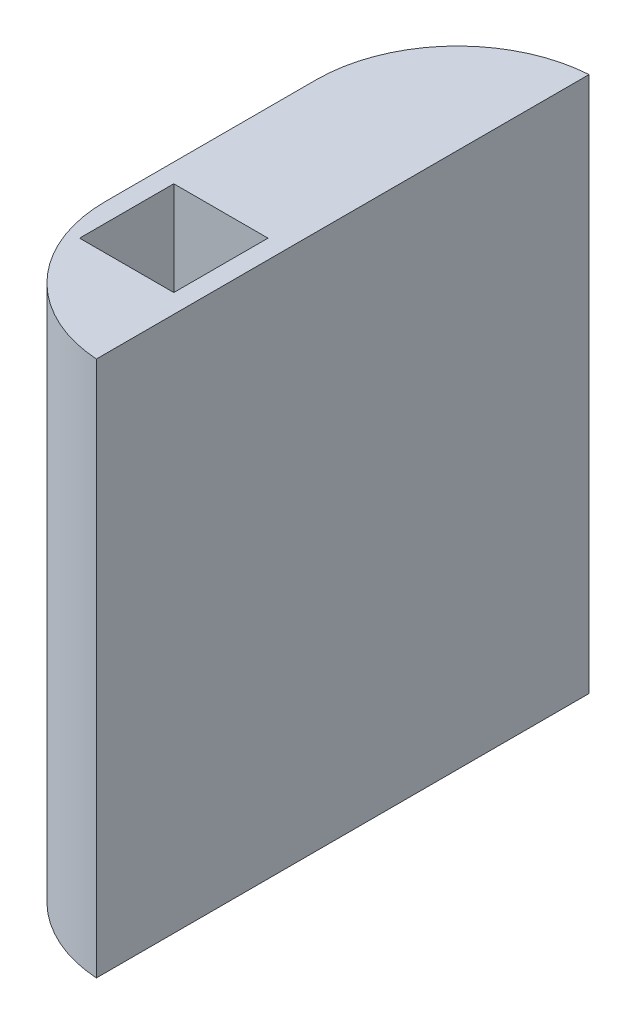
SolidWorks part; units mm, degrees
ref_plane "Спереди" through (0, 0, 0) normal (0, 0, 1) x (1, 0, 0)
ref_plane "Сверху" through (0, 0, 0) normal (0, 1, 0) x (1, 0, 0)
ref_plane "Справа" through (0, 0, 0) normal (1, 0, 0) x (0, 0, -1)
sketch "Эскиз2" plane through (0, 0, 0) normal (0, 1, 0) x (1, 0, 0)
  line L1 (-7, 26.15) -> (7, 26.15)
  line L2 (-7, 26.15) -> (-7, -26.15)
  line L3 (-7, -26.15) -> (7, -26.15)
  line L4 (7, 26.15) -> (7, -26.15)
  line L5 (-7, 26.15) -> (7, -26.15) construction
  line L6 (-7, -26.15) -> (7, 26.15) construction
  point P0 (0, 0)
extrude "Бобышка-Вытянуть1" add sketch "Эскиз2" along normal blind 56.9
sketch "Эскиз3" plane through (0, 56.9, 0) normal (0, 1, 0) x (1, 0, 0)
  line L0 (0, -26.15) -> (0, 26.15)
  line L2 (-7, -26.15) -> (7, -26.15) construction
  line L4 (7, 26.15) -> (-7, 26.15) construction
  line L5 (-7, -26.15) -> (-7, -10.93)
  line L6 (-7, 26.15) -> (-7, -26.15) construction
  line L7 (-7, -10.93) -> (7, -10.93)
  line L8 (7, -26.15) -> (7, 26.15) construction
  line L10 (-5, -5.93) -> (5, -5.93)
  line L11 (-5, -5.93) -> (-5, -15.93)
  line L12 (-5, -15.93) -> (5, -15.93)
  line L13 (5, -5.93) -> (5, -15.93)
  line L14 (-5, -5.93) -> (5, -15.93) construction
  line L15 (-5, -15.93) -> (5, -5.93) construction
  point P13 (0, -10.93)
extrude "Вырез-Вытянуть1" cut sketch "Эскиз3" against normal blind 56.9 contours L11 L12 L0 L7 | L10 L11 L7 L0 | L13 L10 L0 L7 | L13 L7 L0 L12 region at (-2.5, 56.9, 13.43) region at (2.5, 56.9, 13.43) region at (-2.5, 56.9, 8.43) region at (2.5, 56.9, 8.43)
fillet "Скругление6" radius 15 2 edges at (-7, 28.45, -26.15) (-7, 28.45, 26.15)
